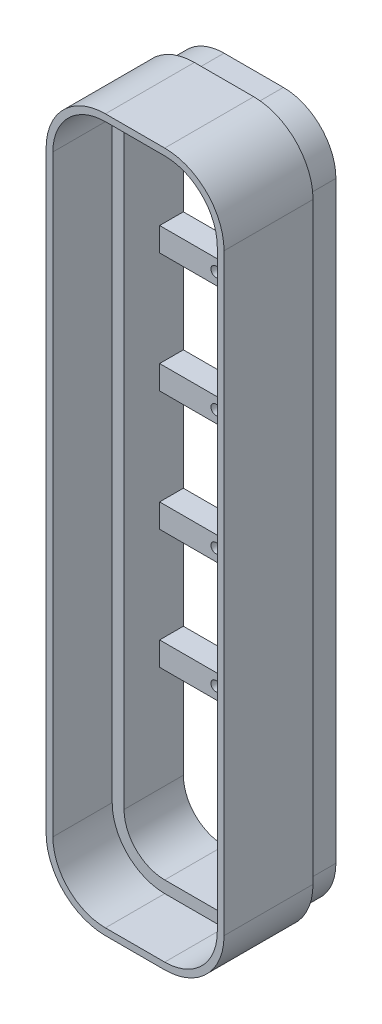
SolidWorks part; units mm, degrees
ref_plane "Front Plane" through (0, 0, 0) normal (0, 0, 1) x (1, 0, 0)
ref_plane "Top Plane" through (0, 0, 0) normal (0, 1, 0) x (1, 0, 0)
ref_plane "Right Plane" through (0, 0, 0) normal (1, 0, 0) x (0, 0, -1)
sketch "Sketch1" plane through (0, 0, 0) normal (0, 0, 1) x (1, 0, 0)
  line L1 (-19.05, -76.2) -> (19.05, -76.2)
  line L2 (-19.05, -76.2) -> (-19.05, 76.2)
  line L3 (-19.05, 76.2) -> (19.05, 76.2)
  line L4 (19.05, -76.2) -> (19.05, 76.2)
  line L5 (-19.05, -76.2) -> (19.05, 76.2) construction
  line L6 (-19.05, 76.2) -> (19.05, -76.2) construction
  point P0 (0, 0)
  dimension "D1" = 38.1
  dimension "D2" = 152.4
extrude "Boss-Extrude1" add sketch "Sketch1" along normal mid plane 25.4
fillet "Fillet1" radius 12.7 4 edges at (19.05, -76.2, 0) (-19.05, -76.2, 0) (19.05, 76.2, 0) (-19.05, 76.2, 0)
sketch "Sketch2" plane through (0, 0, 12.7) normal (0, 0, 1) x (1, 0, 0)
  line L0 (-17.5992, 63.5) -> (-17.5992, -63.5)
  line L1 (-6.35, -74.7492) -> (6.35, -74.7492)
  line L2 (17.5992, -63.5) -> (17.5992, 63.5)
  line L3 (6.35, 74.7492) -> (-6.35, 74.7492)
  line L4 (-6.35, -76.2) -> (6.35, -76.2)
  line L5 (19.05, -63.5) -> (19.05, 63.5)
  line L6 (6.35, 76.2) -> (-6.35, 76.2)
  line L7 (-19.05, 63.5) -> (-19.05, -63.5)
  line L8 (-6.35, -76.2) -> (6.35, -76.2) construction
  line L9 (19.05, -63.5) -> (19.05, 63.5) construction
  line L10 (6.35, 76.2) -> (-6.35, 76.2) construction
  line L11 (-19.05, 63.5) -> (-19.05, -63.5) construction
  arc A0 (-6.35, 74.7492) -> (-17.5992, 63.5) centre (-6.35, 63.5) ccw
  arc A1 (-17.5992, -63.5) -> (-6.35, -74.7492) centre (-6.35, -63.5) ccw
  arc A2 (6.35, -74.7492) -> (17.5992, -63.5) centre (6.35, -63.5) ccw
  arc A3 (17.5992, 63.5) -> (6.35, 74.7492) centre (6.35, 63.5) ccw
  arc A4 (6.35, -76.2) -> (19.05, -63.5) centre (6.35, -63.5) ccw
  arc A5 (19.05, 63.5) -> (6.35, 76.2) centre (6.35, 63.5) ccw
  arc A6 (-6.35, 76.2) -> (-19.05, 63.5) centre (-6.35, 63.5) ccw
  arc A7 (-19.05, -63.5) -> (-6.35, -76.2) centre (-6.35, -63.5) ccw
  arc A8 (6.35, -76.2) -> (19.05, -63.5) centre (6.35, -63.5) ccw construction
  arc A9 (19.05, 63.5) -> (6.35, 76.2) centre (6.35, 63.5) ccw construction
  arc A10 (-6.35, 76.2) -> (-19.05, 63.5) centre (-6.35, 63.5) ccw construction
  arc A11 (-19.05, -63.5) -> (-6.35, -76.2) centre (-6.35, -63.5) ccw construction
  dimension "D1" = 0
  dimension "D2" = 1.4508
extrude "Cut-Extrude1" cut sketch "Sketch2" against normal through all
sketch "Sketch3" plane through (0, 0, -12.7) normal (0, 0, -1) x (-1, 0, 0)
  line L0 (6.35, -74.7492) -> (-6.35, -74.7492) construction
  line L1 (17.5992, 63.5) -> (17.5992, -63.5) construction
  line L2 (-6.35, 74.7492) -> (6.35, 74.7492) construction
  line L3 (-17.5992, -63.5) -> (-17.5992, 63.5) construction
  line L4 (6.35, -74.7492) -> (-6.35, -74.7492)
  line L5 (17.5992, 63.5) -> (17.5992, -63.5)
  line L6 (-6.35, 74.7492) -> (6.35, 74.7492)
  line L7 (-17.5992, -63.5) -> (-17.5992, 63.5)
  arc A0 (-17.5992, -63.5) -> (-6.35, -74.7492) centre (-6.35, -63.5) ccw construction
  arc A1 (6.35, -74.7492) -> (17.5992, -63.5) centre (6.35, -63.5) ccw construction
  arc A2 (17.5992, 63.5) -> (6.35, 74.7492) centre (6.35, 63.5) ccw construction
  arc A3 (-6.35, 74.7492) -> (-17.5992, 63.5) centre (-6.35, 63.5) ccw construction
  arc A4 (-17.5992, -63.5) -> (-6.35, -74.7492) centre (-6.35, -63.5) ccw
  arc A5 (6.35, -74.7492) -> (17.5992, -63.5) centre (6.35, -63.5) ccw
  arc A6 (17.5992, 63.5) -> (6.35, 74.7492) centre (6.35, 63.5) ccw
  arc A7 (-6.35, 74.7492) -> (-17.5992, 63.5) centre (-6.35, 63.5) ccw
extrude "Extrude-Thin1" add sketch "Sketch3" against normal blind 12.7 thin thin type one direction reverse wall 2.54
sketch "Sketch4" plane through (0, 0, -12.7) normal (0, 0, -1) x (-1, 0, 0)
  line L0 (6.35, -76.2) -> (-6.35, -76.2) construction
  line L1 (19.05, 63.5) -> (19.05, -63.5) construction
  line L2 (-19.05, -63.5) -> (-19.05, 63.5) construction
  line L3 (-6.35, 76.2) -> (6.35, 76.2) construction
  line L4 (6.35, -76.2) -> (-6.35, -76.2)
  line L5 (19.05, 63.5) -> (19.05, -63.5)
  line L6 (-19.05, -63.5) -> (-19.05, 63.5)
  line L7 (-6.35, 76.2) -> (6.35, 76.2)
  line L8 (-17.5992, -63.5) -> (-17.5992, 63.5)
  line L9 (-6.35, 74.7492) -> (6.35, 74.7492)
  line L10 (17.5992, 63.5) -> (17.5992, -63.5)
  line L11 (6.35, -74.7492) -> (-6.35, -74.7492)
  arc A0 (-19.05, -63.5) -> (-6.35, -76.2) centre (-6.35, -63.5) ccw construction
  arc A1 (6.35, -76.2) -> (19.05, -63.5) centre (6.35, -63.5) ccw construction
  arc A2 (19.05, 63.5) -> (6.35, 76.2) centre (6.35, 63.5) ccw construction
  arc A3 (-6.35, 76.2) -> (-19.05, 63.5) centre (-6.35, 63.5) ccw construction
  arc A4 (-19.05, -63.5) -> (-6.35, -76.2) centre (-6.35, -63.5) ccw
  arc A5 (6.35, -76.2) -> (19.05, -63.5) centre (6.35, -63.5) ccw
  arc A6 (19.05, 63.5) -> (6.35, 76.2) centre (6.35, 63.5) ccw
  arc A7 (-6.35, 76.2) -> (-19.05, 63.5) centre (-6.35, 63.5) ccw
  arc A8 (-6.35, 74.7492) -> (-17.5992, 63.5) centre (-6.35, 63.5) ccw
  arc A9 (17.5992, 63.5) -> (6.35, 74.7492) centre (6.35, 63.5) ccw
  arc A10 (6.35, -74.7492) -> (17.5992, -63.5) centre (6.35, -63.5) ccw
  arc A11 (-17.5992, -63.5) -> (-6.35, -74.7492) centre (-6.35, -63.5) ccw
  dimension "D1" = 1.4508
extrude "Cut-Extrude2" cut sketch "Sketch4" against normal blind 6.35
ref_plane "Plane1" through (0, 0, -7.62) normal (0, 0, -1) x (-1, 0, 0)
sketch "Sketch6" plane through (0, 0, -7.62) normal (0, 0, -1) x (-1, 0, 0)
  line L0 (17.5992, -63.5) -> (17.5992, 63.5) construction
  line L1 (-17.5992, 35.8915) -> (17.5992, 35.8915)
  line L2 (-17.5992, 35.8915) -> (-17.5992, 40.9715)
  line L3 (-17.5992, 40.9715) -> (17.5992, 40.9715)
  line L4 (17.5992, 35.8915) -> (17.5992, 40.9715)
  line L5 (-17.5992, 35.8915) -> (17.5992, 40.9715) construction
  line L6 (-17.5992, 40.9715) -> (17.5992, 35.8915) construction
  line L7 (17.5992, -63.5) -> (17.5992, 63.5) construction
  line L8 (-17.5992, 10.299) -> (17.5992, 10.299)
  line L9 (-17.5992, 10.299) -> (-17.5992, 15.379)
  line L10 (-17.5992, 15.379) -> (17.5992, 15.379)
  line L11 (17.5992, 10.299) -> (17.5992, 15.379)
  line L12 (-17.5992, 10.299) -> (17.5992, 15.379) construction
  line L13 (-17.5992, 15.379) -> (17.5992, 10.299) construction
  line L14 (-17.5992, 63.5) -> (-17.5992, -63.5) construction
  line L15 (-17.5992, -15.3585) -> (17.5992, -15.3585)
  line L16 (-17.5992, -15.3585) -> (-17.5992, -10.2785)
  line L17 (-17.5992, -10.2785) -> (17.5992, -10.2785)
  line L18 (17.5992, -15.3585) -> (17.5992, -10.2785)
  line L19 (-17.5992, -15.3585) -> (17.5992, -10.2785) construction
  line L20 (-17.5992, -10.2785) -> (17.5992, -15.3585) construction
  line L21 (-17.5992, -40.951) -> (17.5992, -40.951)
  line L22 (-17.5992, -40.951) -> (-17.5992, -35.871)
  line L23 (-17.5992, -35.871) -> (17.5992, -35.871)
  line L24 (17.5992, -40.951) -> (17.5992, -35.871)
  line L25 (-17.5992, -40.951) -> (17.5992, -35.871) construction
  line L26 (-17.5992, -35.871) -> (17.5992, -40.951) construction
  circle A0 centre (3.0157, -38.411) radius 1.0543 construction
  circle A1 centre (3.0157, -12.8185) radius 1.0543 construction
  circle A2 centre (3.0157, 12.839) radius 1.0543 construction
  circle A3 centre (3.0157, 38.4315) radius 1.0543 construction
  circle A4 centre (3.0157, -38.411) radius 1.0543
  circle A5 centre (3.0157, -12.8185) radius 1.0543
  circle A6 centre (3.0157, 12.839) radius 1.0543
  circle A7 centre (3.0157, 38.4315) radius 1.0543
  point P12 (0, 38.4315)
  point P19 (0, 12.839)
  point P26 (0, -12.8185)
  point P31 (0, -38.411)
  point P36 (0, 0)
  point P37 (0, 0)
  point P38 (0, 0)
  point P39 (0, 0)
  dimension "D1" = 5.08
extrude "Boss-Extrude2" add sketch "Sketch6" along normal up to surface (5.08 mm away) up to face at (0, 0, -12.7)
